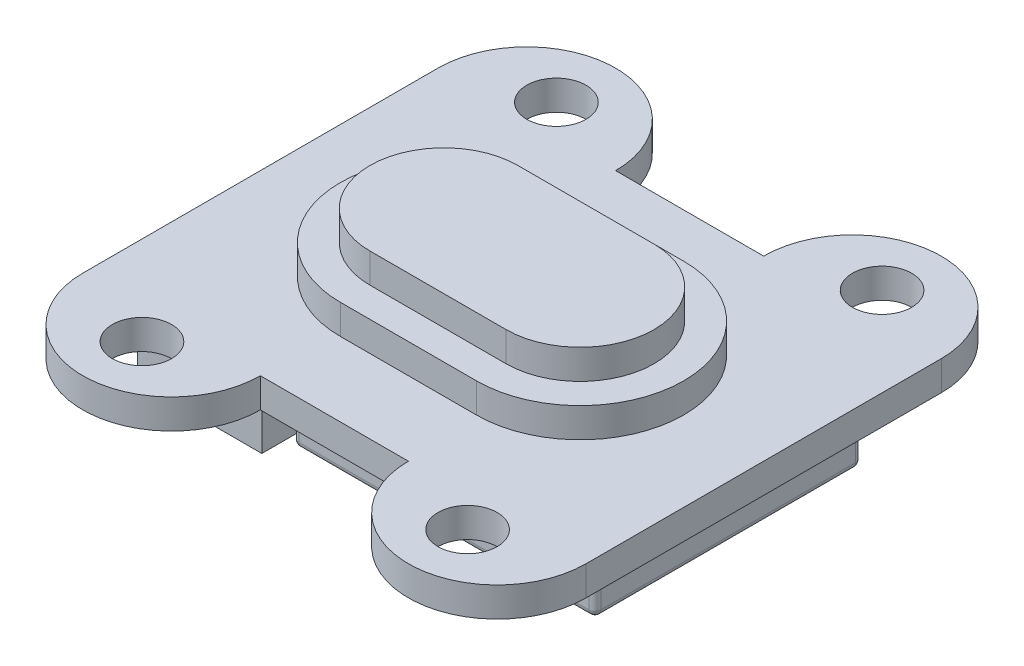
SolidWorks part; units mm, degrees
ref_plane "前视基准面" through (0, 0, 0) normal (0, 0, 1) x (1, 0, 0)
ref_plane "上视基准面" through (0, 0, 0) normal (0, 1, 0) x (1, 0, 0)
ref_plane "右视基准面" through (0, 0, 0) normal (1, 0, 0) x (0, 0, -1)
sketch "草图1" plane through (0, 0, 0) normal (0, 1, 0) x (1, 0, 0)
  line L0 (-5.5, 6) -> (5.5, 6) construction
  line L1 (8.5, -6) -> (-8.5, -6)
  line L2 (8.5, -6) -> (8.5, 6)
  line L3 (8.5, 6) -> (-8.5, 6)
  line L4 (-8.5, -6) -> (-8.5, 6)
  line L5 (8.5, -6) -> (-8.5, 6) construction
  line L6 (8.5, 6) -> (-8.5, -6) construction
  line L7 (0, 0) -> (4.2281, 0) construction
  line L8 (5.5, 7) -> (5.5, -7) construction
  line L9 (0, 0) -> (0, 3.0316) construction
  circle A0 centre (-5.5, 6) radius 3
  circle A1 centre (5.5, 6) radius 3
  circle A2 centre (-5.5, -6) radius 3
  circle A3 centre (5.5, -6) radius 3
  circle A4 centre (5.5, 7) radius 1
  circle A5 centre (5.5, -7) radius 1
  circle A6 centre (-5.5, -7) radius 1
  circle A7 centre (-5.5, 7) radius 1
  point P0 (0, 0)
  point P10 (0, 6)
  point P21 (5.5, 0)
  dimension "D4" = 6
  dimension "D5" = 6
  dimension "D7" = 2
  dimension "D1" = 17
  dimension "D2" = 12
  dimension "D3" = 11
  dimension "D6" = 14
extrude "凸台-拉伸1" add sketch "草图1" along normal blind 1 contours L3 A7 A0 | L3 A0 | L1 A3 L2 A1 L3 A0 L4 A2 | A2 L1 | L1 A6 A2 | A3 L1 | L1 A5 A3 | L3 A4 A1 | L3 A1 region at (5.5, 0, 8.9329) region at (0, 0, 0) region at (5.5, 0, 4.7268) region at (5.5, 0, -4.7268) region at (7, 0, -6.0671) region at (-5.5, 0, 8.9329) region at (-5.5, 0, 4.7268) region at (-5.5, 0, -4.7268) region at (-4, 0, -6.0671)
sketch "草图3" plane through (0, 1, 0) normal (0, 1, 0) x (1, 0, 0)
  line L0 (-2.3, 0) -> (2.3, 0) construction
  line L1 (-2.3, 2.5) -> (2.3, 2.5)
  line L2 (-2.3, -2.5) -> (2.3, -2.5)
  line L3 (-2.3, 0) -> (2.3, 0) construction
  line L4 (-2.3, 3.5) -> (2.3, 3.5)
  line L5 (-2.3, -3.5) -> (2.3, -3.5)
  arc A0 (-2.3, 2.5) -> (-2.3, -2.5) centre (-2.3, 0) ccw
  arc A1 (2.3, -2.5) -> (2.3, 2.5) centre (2.3, 0) ccw
  arc A2 (-2.3, 3.5) -> (-2.3, -3.5) centre (-2.3, 0) ccw
  arc A3 (2.3, -3.5) -> (2.3, 3.5) centre (2.3, 0) ccw
  point P2 (0, 0)
  point P8 (-4.8, 0)
  point P9 (4.8, 0)
  point P12 (0, 0)
  point P17 (-5.8, 0)
  point P18 (5.8, 0)
  dimension "D2" = 9.6
  dimension "D1" = 5
  dimension "D3" = 7
  dimension "D4" = 11.6
extrude "凸台-拉伸2" add sketch "草图3" along normal blind 1 contours L5 A3 L4 A2 A1 L2 A0 L1 region at (0, 1, -3.3645)
extrude "凸台-拉伸3" add sketch "草图3<3>" along normal blind 2 contours A0 L2 A1 L1
sketch "草图3<3>" plane through (0, 1, 0) normal (0, 1, 0) x (1, 0, 0) same geometry as "草图3"
sketch "草图5" plane through (0, 0, 0) normal (0, -1, 0) x (1, 0, 0)
  line L0 (-2.9, 0) -> (-4.3, 0) construction
  line L1 (-2.9, 4.5) -> (7.3, 4.5)
  line L2 (-2.9, 4.5) -> (-2.9, -4.5)
  line L3 (-2.9, -4.5) -> (7.3, -4.5)
  line L4 (7.3, 4.5) -> (7.3, -4.5)
  line L5 (-2.9, 4.5) -> (7.3, -4.5) construction
  line L6 (-2.9, -4.5) -> (7.3, 4.5) construction
  line L7 (-8.5, 6) -> (-8.5, -6) construction
  line L8 (-8.5, 4.15) -> (-4.3, 4.15)
  line L9 (-8.5, 4.15) -> (-8.5, -4.15)
  line L10 (-8.5, -4.15) -> (-4.3, -4.15)
  line L11 (-4.3, 4.15) -> (-4.3, -4.15)
  line L12 (-8.5, 4.15) -> (-4.3, -4.15) construction
  line L13 (-8.5, -4.15) -> (-4.3, 4.15) construction
  point P0 (2.2, 0)
  point P5 (-6.4, 0)
  dimension "D1" = 10.2
  dimension "D2" = 9
  dimension "D3" = 1.4
  dimension "D4" = 8.3
  dimension "D5" = 4.2
extrude "凸台-拉伸4" add sketch "草图5" along normal blind 2 contours L4 L1 L2 L3 region at (2.2, 0, 0)
extrude "凸台-拉伸5" add sketch "草图5<3>" along normal blind 3.1 separate body contours L8 L11 L10 L9
sketch "草图5<3>" plane through (0, 0, 0) normal (0, -1, 0) x (1, 0, 0) same geometry as "草图5"
shell "抽壳1" thickness 0.5 removed face at (-8.5, -1.55, 0)
sketch "草图6" plane through (-4.8, 0, 0) normal (-1, 0, 0) x (0, 0, 1)
  line L1 (3.65, -0.5) -> (-3.65, -0.5) construction
  line L2 (1.4, -1.9) -> (1.4, -2.1)
  line L3 (3.65, -0.5) -> (-3.65, -0.5) construction
  line L4 (0, -0.5) -> (0, -2) construction
  line L5 (0, -2) -> (2.5, -2) construction
  line L6 (1.4, -1.9) -> (1.6, -1.9)
  line L7 (2.4, -1.9) -> (2.6, -1.9)
  line L8 (2.4, -1.9) -> (2.4, -2.1)
  line L9 (2.4, -2.1) -> (2.6, -2.1)
  line L10 (2.6, -1.9) -> (2.6, -2.1)
  line L11 (2.4, -1.9) -> (2.6, -2.1) construction
  line L12 (2.4, -2.1) -> (2.6, -1.9) construction
  line L13 (1.6, -1.9) -> (1.6, -2.1)
  line L14 (1.4, -2.1) -> (1.6, -2.1)
  line L15 (0.4, -1.9) -> (0.4, -2.1)
  line L16 (0.4, -1.9) -> (0.6, -1.9)
  line L17 (0.6, -1.9) -> (0.6, -2.1)
  line L18 (0.4, -2.1) -> (0.6, -2.1)
  line L19 (-0.6, -1.9) -> (-0.6, -2.1)
  line L20 (-0.6, -1.9) -> (-0.4, -1.9)
  line L21 (-0.4, -1.9) -> (-0.4, -2.1)
  line L22 (-0.6, -2.1) -> (-0.4, -2.1)
  line L23 (-1.6, -1.9) -> (-1.6, -2.1)
  line L24 (-1.6, -1.9) -> (-1.4, -1.9)
  line L25 (-1.4, -1.9) -> (-1.4, -2.1)
  line L26 (-1.6, -2.1) -> (-1.4, -2.1)
  line L27 (-2.6, -1.9) -> (-2.6, -2.1)
  line L28 (-2.6, -1.9) -> (-2.4, -1.9)
  line L29 (-2.4, -1.9) -> (-2.4, -2.1)
  line L30 (-2.6, -2.1) -> (-2.4, -2.1)
  dimension "D1" = 2.5
  dimension "D2" = 0.2
  dimension "D3" = 1.5
  dimension "D4" = 6
extrude "凸台-拉伸6" add sketch "草图6" along normal blind 2
fillet "圆角1" radius 0.2 8 edges at (-2.9, -2, 0) (2.2, -2, -4.5) (7.3, -2, 0) (2.2, -2, 4.5) (-2.9, -1, -4.5) (-2.9, -1, 4.5) (7.3, -1, -4.5) (7.3, -1, 4.5)
